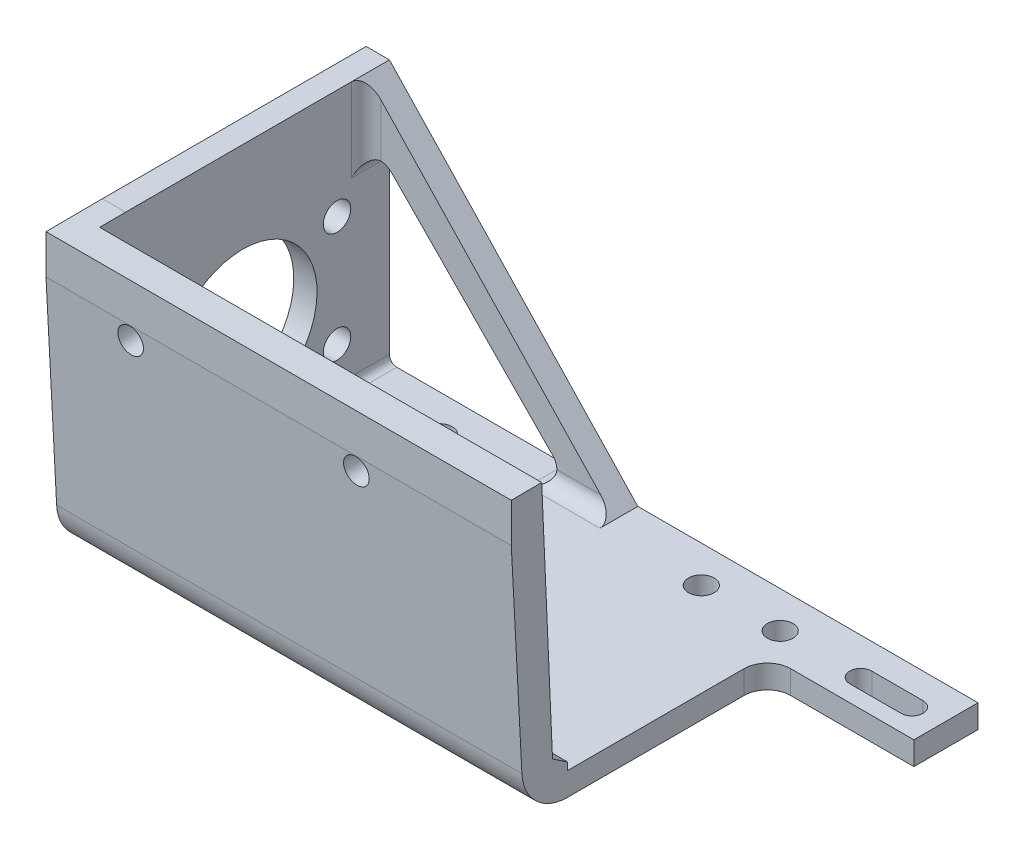
SolidWorks part; units mm, degrees
ref_plane "Front Plane" through (0, 0, 0) normal (0, 0, 1) x (1, 0, 0)
ref_plane "Top Plane" through (0, 0, 0) normal (0, 1, 0) x (1, 0, 0)
ref_plane "Right Plane" through (0, 0, 0) normal (1, 0, 0) x (0, 0, -1)
sketch "Sketch2" plane through (0, 0, 0) normal (0, 0, 1) x (1, 0, 0)
  line L0 (6.35, 78) -> (80, 0.1684)
  line L1 (0, 0) -> (6.35, 0)
  line L2 (0, 0) -> (0, 78)
  line L3 (0, 78) -> (6.35, 78)
  line L4 (6.35, 0) -> (6.35, 65.0327)
  line L6 (6.35, 65.0327) -> (70, 0.1684)
  line L7 (70, 0.1684) -> (80, 0.1684)
  dimension "D1" = 6.35
  dimension "D2" = 78
  dimension "D3" = 80
  dimension "D4" = 10
extrude "Boss-Extrude1" add sketch "Sketch2" along normal blind 80
sketch "Sketch3" plane through (6.35, 0, 0) normal (1, 0, 0) x (0, 0, -1)
  line L0 (0, 0) -> (0, 65.0327) construction
  line L1 (-80, 0) -> (0, 0)
  line L2 (-80, 0) -> (-80, 6.35)
  line L3 (-80, 6.35) -> (0, 6.35)
  line L4 (0, 0) -> (0, 6.35)
  dimension "D1" = 6.35
extrude "Boss-Extrude2" add sketch "Sketch3" along normal blind 160.65
sketch "Sketch8" plane through (0, 6.35, 0) normal (0, 1, 0) x (1, 0, 0)
  line L0 (167, 0) -> (74.1505, 0) construction
  line L1 (6.35, -80) -> (94.6764, -80)
  line L2 (6.35, -80) -> (6.35, -6.35)
  line L3 (6.35, -6.35) -> (94.6764, -6.35)
  line L4 (94.6764, -80) -> (94.6764, -6.35)
  dimension "D1" = 6.35
extrude "Cut-Extrude2" cut sketch "Sketch8" along normal up to next
sketch "Sketch9" plane through (0, 6.35, 0) normal (0, 1, 0) x (1, 0, 0)
  line L1 (167, -80) -> (0, -80)
  line L2 (167, -80) -> (167, -72)
  line L3 (167, -72) -> (0, -72)
  line L4 (0, -80) -> (0, -72)
extrude "Cut-Extrude4" cut sketch "Sketch9" against normal through all both and the other way through all
sketch "Sketch10" plane through (0, 6.35, 0) normal (0, 1, 0) x (1, 0, 0)
  line L0 (167, 0) -> (74.1505, 0) construction
  line L1 (167, -72) -> (127, -72)
  line L2 (167, -72) -> (167, -17.5)
  line L3 (167, -17.5) -> (127, -17.5)
  line L4 (127, -72) -> (127, -17.5)
  dimension "D1" = 17.5
extrude "Cut-Extrude5" cut sketch "Sketch10" against normal up to next
sketch "Sketch11" plane through (0, 6.35, 0) normal (0, 1, 0) x (1, 0, 0)
  line L0 (159, -10) -> (145, -10) construction
  line L1 (159, -13) -> (145, -13)
  line L2 (159, -7) -> (145, -7)
  line L3 (167, 0) -> (167, -17.5) construction
  line L4 (167, 0) -> (74.1505, 0) construction
  line L5 (0, -72) -> (0, 0) construction
  arc A0 (159, -13) -> (159, -7) centre (159, -10) ccw
  arc A1 (145, -7) -> (145, -13) centre (145, -10) ccw
  circle A2 centre (123, -10) radius 3.5
  circle A3 centre (101.48, -10) radius 3.5
  circle A6 centre (101.48, -62) radius 3.5
  circle A9 centre (30, -10) radius 3.5
  point P2 (152, -10)
  point P7 (162, -10)
  dimension "D1" = 14
  dimension "D4" = 30
  dimension "D5" = 22
  dimension "D9" = 65.52
  dimension "D2" = 5
  dimension "D3" = 7
extrude "Cut-Extrude6" cut sketch "Sketch11" against normal up to next
sketch "Sketch12" plane through (6.35, 0, 0) normal (1, 0, 0) x (0, 0, -1)
  line L0 (0, 6.35) -> (0, 65.0327) construction
  line L2 (0, 6.35) -> (-72, 6.35) construction
  circle A0 centre (-66.64, 15.3315) radius 3.75
  circle A1 centre (-66.64, 48.1711) radius 3.75
  circle A2 centre (-14.3, 48.12) radius 3.75
  circle A3 centre (-14.3, 17.9) radius 3.75
  circle A4 centre (-40, 33) radius 20.25
  dimension "D1" = 40
  dimension "D2" = 26.65
  dimension "D3" = 52.34
  dimension "D4" = 30.22
  dimension "D5" = 11.55
  dimension "D6" = 14.3
extrude "Cut-Extrude7" cut sketch "Sketch12" against normal up to next
fillet "Fillet1" radius 4 1 edges at (6.35, 71.5164, 6.35)
fillet "Fillet2" radius 4 1 edges at (6.35, 65.0327, 5.175)
fillet "Fillet3" radius 4 1 edges at (69.0423, 6.35, 6.35)
fillet "Fillet4" radius 4 1 edges at (63.9342, 6.35, 5.175)
fillet "Fillet5" radius 2 1 edges at (6.35, 6.35, 36)
fillet "Fillet6" radius 6.35 1 edges at (127, 3.175, 17.5)
sketch "Sketch17" plane through (0, 0, 0) normal (-1, 0, 0) x (0, 0, 1)
  line L0 (87.3842, 67.2065) -> (84.4829, 11.8458) construction
  line L1 (87.3842, 67.2065) -> (84.4829, 11.8458)
  line L2 (87.3842, 67.2065) -> (87.3842, 77.9122)
  line L3 (87.3842, 77.9122) -> (72, 78)
  line L4 (72, 78) -> (72, 0)
  arc A0 (72, 0) -> (84.4829, 11.8458) centre (72, 12.5) ccw construction
  arc A1 (72, 0) -> (84.4829, 11.8458) centre (72, 12.5) ccw
extrude "Boss-Extrude3" add sketch "Sketch17" against normal up to surface (6.35 mm away) up to face at (6.35, 51.9211, 66.64)
sketch "Sketch18" plane through (6.35, 0, 0) normal (1, 0, 0) x (0, 0, -1)
  line L0 (-87.3842, 77.9122) -> (-87.3842, 67.2065) construction
  line L1 (-87.3842, 67.2065) -> (-84.4829, 11.8458) construction
  line L2 (-87.3842, 77.9122) -> (-87.3842, 67.2065)
  line L3 (-87.3842, 67.2065) -> (-84.4829, 11.8458)
  line L4 (-87.3842, 77.9122) -> (-79.0854, 77.9596)
  line L5 (-72, 78) -> (-87.3842, 77.9122) construction
  line L6 (-79.0854, 77.9596) -> (-76.1342, 11.1534)
  line L7 (-76.1342, 11.1534) -> (-72, 8.35)
  line L8 (-72, 8.35) -> (-72, 0)
  arc A0 (-84.4829, 11.8458) -> (-72, 0) centre (-72, 12.5) ccw construction
  arc A1 (-84.4829, 11.8458) -> (-72, 0) centre (-72, 12.5) ccw
extrude "Boss-Extrude4" add sketch "Sketch18" along normal up to surface (120.65 mm away) up to face at (127, 3.175, 47.925)
sketch "Sketch20" plane through (0, -3.335, 75.4942) normal (0, 0.0441, -0.999) x (-1, 0, 0)
  line L0 (-127, 81.3738) -> (-6.35, 81.3738) construction
  circle A0 centre (-84.5356, 67.3238) radius 3.5
  circle A1 centre (-22.9043, 67.3238) radius 3.5
  dimension "D1" = 14.05
extrude "Cut-Extrude8" cut sketch "Sketch20" against normal up to surface (8.7638 mm away) up to face at (63.5, 39.5262, 85.9335)
sketch "Sketch21" plane through (0, 0, 0) normal (0, -1, 0) x (1, 0, 0)
  line L1 (0, 0) -> (205.7495, 0)
  line L2 (0, 0) -> (0, 138.282)
  line L3 (0, 138.282) -> (205.7495, 138.282)
  line L4 (205.7495, 0) -> (205.7495, 138.282)
